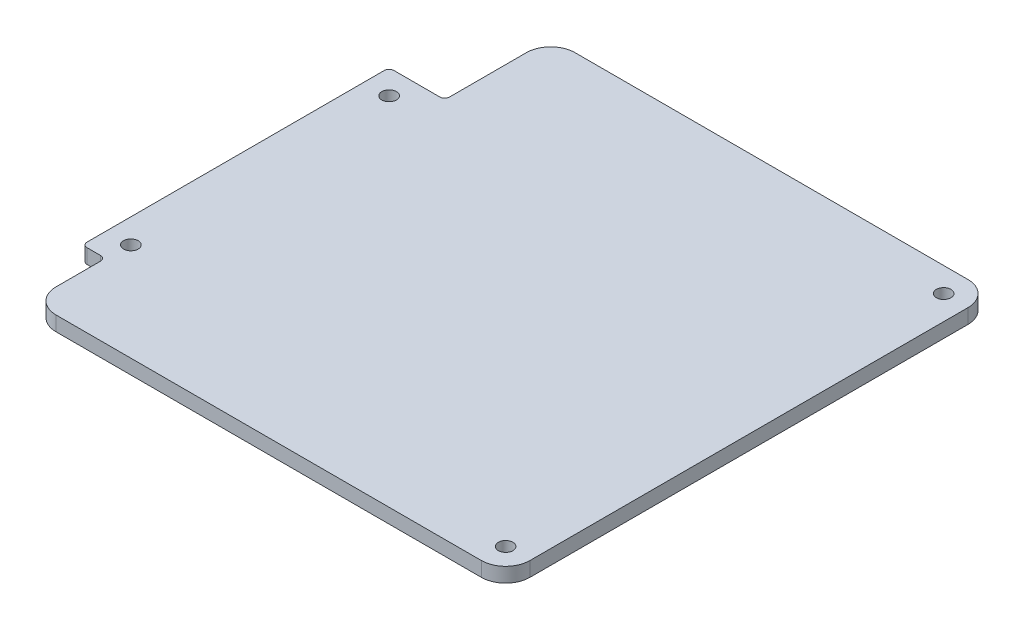
SolidWorks part; units mm, degrees
ref_plane "Front Plane" through (0, 0, 0) normal (0, 0, 1) x (1, 0, 0)
ref_plane "Top Plane" through (0, 0, 0) normal (0, 1, 0) x (1, 0, 0)
ref_plane "Right Plane" through (0, 0, 0) normal (1, 0, 0) x (0, 0, -1)
ref_plane "Plane1" through (0, 23, 0) normal (0, 1, 0) x (1, 0, 0)
sketch "Sketch1" plane through (0, 23, 0) normal (0, 1, 0) x (1, 0, 0)
  line L0 (98.3054, 50) -> (98.3054, 28.2195)
  line L1 (189.0458, 50) -> (98.3054, 50)
  line L2 (189.0458, 50) -> (189.0458, -50)
  line L3 (189.0458, -50) -> (97.6502, -50)
  line L5 (98.3054, 28.2195) -> (86.88, 28.2195)
  line L6 (86.88, 28.2195) -> (86.88, -34.8422)
  line L7 (86.88, -34.8422) -> (91.6598, -34.8422)
  line L8 (91.6598, -34.8422) -> (91.6598, -50)
  line L9 (91.6598, -50) -> (97.6502, -50)
  line L10 (94.8054, 33.2195) -> (98.3054, 33.2195) construction
  line L11 (184.0458, 45) -> (184.0458, 50) construction
  line L12 (93.3054, 31.7195) -> (93.3054, 28.2195) construction
  line L13 (99.4745, -34.8422) -> (86.1225, -34.8422) construction
  line L14 (88.1598, -39.8422) -> (91.6598, -39.8422) construction
  line L15 (86.6598, -38.3422) -> (86.6598, -34.8422) construction
  line L16 (189.0458, 0) -> (190, 0) construction
  line L17 (190, -60) -> (190, 60) construction
  line L18 (105.0183, -40) -> (185.0183, -40) construction
  line L19 (105.0183, -40) -> (105.0183, 40) construction
  line L20 (105.0183, 40) -> (185.0183, 40) construction
  line L21 (185.0183, -40) -> (185.0183, 40) construction
  line L22 (184.0458, 45) -> (189.0458, 45) construction
  line L23 (184.0458, -45) -> (189.0458, -45) construction
  line L24 (184.0458, -45) -> (184.0458, -50) construction
  line L25 (91.88, 23.2195) -> (91.88, 28.2195) construction
  line L26 (91.88, 23.2195) -> (86.88, 23.2195) construction
  line L27 (91.88, -29.8422) -> (91.88, -34.8422) construction
  line L28 (91.88, -29.8422) -> (86.88, -29.8422) construction
  circle A0 centre (86.6598, -39.8422) radius 1.5 construction
  circle A1 centre (93.3054, 33.2195) radius 1.5 construction
  circle A2 centre (184.0458, 45) radius 1.5 construction
  circle A3 centre (184.0458, 45) radius 1.5 construction
  circle A4 centre (184.0458, -45) radius 1.5 construction
  circle A6 centre (91.88, 23.2195) radius 1.5 construction
  circle A7 centre (91.88, -29.8422) radius 1.5 construction
  point P32 (185.0183, 0)
  dimension "D1" = 100
  dimension "D2" = 80
  dimension "D3" = 3.5
  dimension "D4" = 5
extrude "Boss-Extrude1" add sketch "Sketch1" along normal blind 3
fillet "Fillet3" radius 5 4 edges at (189.0458, 24.5, -50) (98.3054, 24.5, -50) (91.6598, 24.5, 50) (189.0458, 24.5, 50)
fillet "Fillet2" radius 1 4 edges at (86.88, 24.5, -28.2195) (98.3054, 24.5, -28.2195) (91.6598, 24.5, 34.8422) (86.88, 24.5, 34.8422)
sketch "Sketch2" plane through (0, 23, 0) normal (0, 1, 0) x (1, 0, 0)
  circle A0 centre (184.0458, -45) radius 1.5 construction
  circle A1 centre (184.0458, -45) radius 1.5
  circle A2 centre (91.88, -29.8422) radius 1.5 construction
  circle A3 centre (91.88, -29.8422) radius 1.5
  circle A4 centre (91.88, 23.2195) radius 1.5 construction
  circle A5 centre (91.88, 23.2195) radius 1.5
  circle A6 centre (184.0458, 45) radius 1.5 construction
  circle A7 centre (184.0458, 45) radius 1.5
extrude "Cut-Extrude1" cut sketch "Sketch2" along normal up to surface (3 mm away) up to face at (116.4727, 26, 1.6557)
